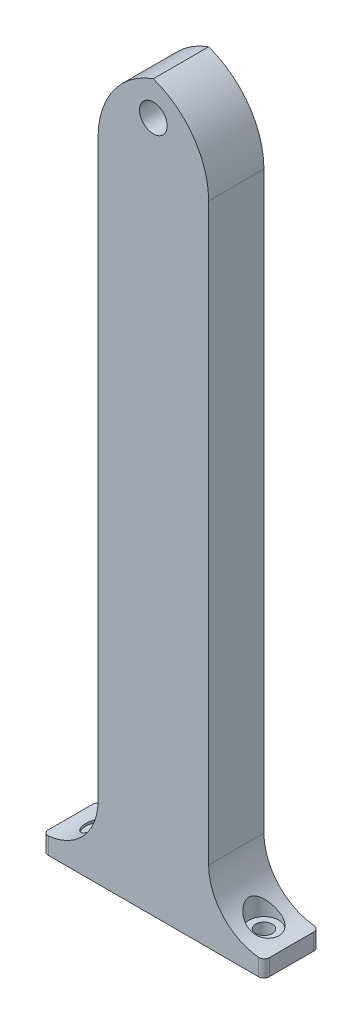
SolidWorks part; units mm, degrees
ref_plane "Front Plane" through (0, 0, 0) normal (0, 0, 1) x (1, 0, 0)
ref_plane "Top Plane" through (0, 0, 0) normal (0, 1, 0) x (1, 0, 0)
ref_plane "Right Plane" through (0, 0, 0) normal (1, 0, 0) x (0, 0, -1)
sketch "Sketch2" plane through (0, 0, 0) normal (0, 1, 0) x (1, 0, 0)
  line L1 (10, -5) -> (-10, -5)
  line L2 (10, -5) -> (10, 5)
  line L3 (10, 5) -> (-10, 5)
  line L4 (-10, -5) -> (-10, 5)
  line L5 (10, -5) -> (-10, 5) construction
  line L6 (10, 5) -> (-10, -5) construction
  point P0 (0, 0)
  dimension "D1" = 10
  dimension "D2" = 20
extrude "Boss-Extrude1" add sketch "Sketch2" along normal blind 132
sketch "Sketch6" plane through (10, 0, 0) normal (1, 0, 0) x (0, 0, -1)
  line L0 (5, 132) -> (5, 0) construction
  line L1 (-5, 0) -> (5, 0)
  line L2 (-5, 0) -> (-5, 3)
  line L3 (-5, 3) -> (5, 3)
  line L4 (5, 0) -> (5, 3)
  dimension "D1" = 3
extrude "Boss-Extrude2" add sketch "Sketch6" along normal blind 10
ref_plane "Plane1" through (0, 3, 0) normal (0, 1, 0) x (1, 0, 0)
fillet "Fillet2" radius 10 1 edges at (10, 3, 0)
sketch "Sketch19" plane through (0, 3, 0) normal (0, 1, 0) x (1, 0, 0)
  line L0 (15, 5) -> (15, -5) construction
  line L1 (10, -5) -> (20, -5) construction
  line L2 (20, 5) -> (10, 5) construction
  circle A0 centre (15, 0) radius 1.5
  circle A1 centre (15, 0) radius 2.7
  dimension "D1" = 3
  dimension "D2" = 5.4
extrude "Cut-Extrude5" cut sketch "Sketch19" against normal through all both and the other way through all contours A0
extrude "Cut-Extrude7" cut sketch "Sketch19<5>" along normal through all
sketch "Sketch19<5>" plane through (0, 3, 0) normal (0, 1, 0) x (1, 0, 0) same geometry as "Sketch19"
mirror "Mirror16" about plane through (0, 0, 0) normal (1, 0, 0) of "Boss-Extrude2"
fillet "Fillet1" radius 1 4 edges at (20, 1.5, -5) (20, 1.5, 5) (-20, 1.5, -5) (-20, 1.5, 5)
fillet "Fillet3" radius 10 1 edges at (-10, 3, 0)
sketch "Sketch20" plane through (0, 3, 0) normal (0, 1, 0) x (1, 0, 0)
  line L0 (-14.5, 5) -> (-14.5, -5) construction
  line L1 (-10, 5) -> (-19, 5) construction
  line L2 (-19, -5) -> (-10, -5) construction
  circle A0 centre (-14.5, 0) radius 1.5
  circle A1 centre (-14.5, 0) radius 2.7
  dimension "D1" = 3
  dimension "D2" = 5.4
extrude "Cut-Extrude8" cut sketch "Sketch20" against normal through all both and the other way through all contours A0
extrude "Cut-Extrude9" cut sketch "Sketch20<3>" along normal through all
sketch "Sketch20<3>" plane through (0, 3, 0) normal (0, 1, 0) x (1, 0, 0) same geometry as "Sketch20"
sketch "Sketch21" plane through (0, 0, 5) normal (0, 0, 1) x (1, 0, 0)
  line L0 (0, 0) -> (0, 125) construction
  circle A0 centre (0, 125) radius 2.5
  dimension "D2" = 5
  dimension "D1" = 125
extrude "Cut-Extrude10" cut sketch "Sketch21" against normal up to surface (10 mm away) up to face at (0, 36.5792, -5)
fillet "Fillet4" radius 15 2 edges at (-10, 132, 0) (10, 132, 0)
